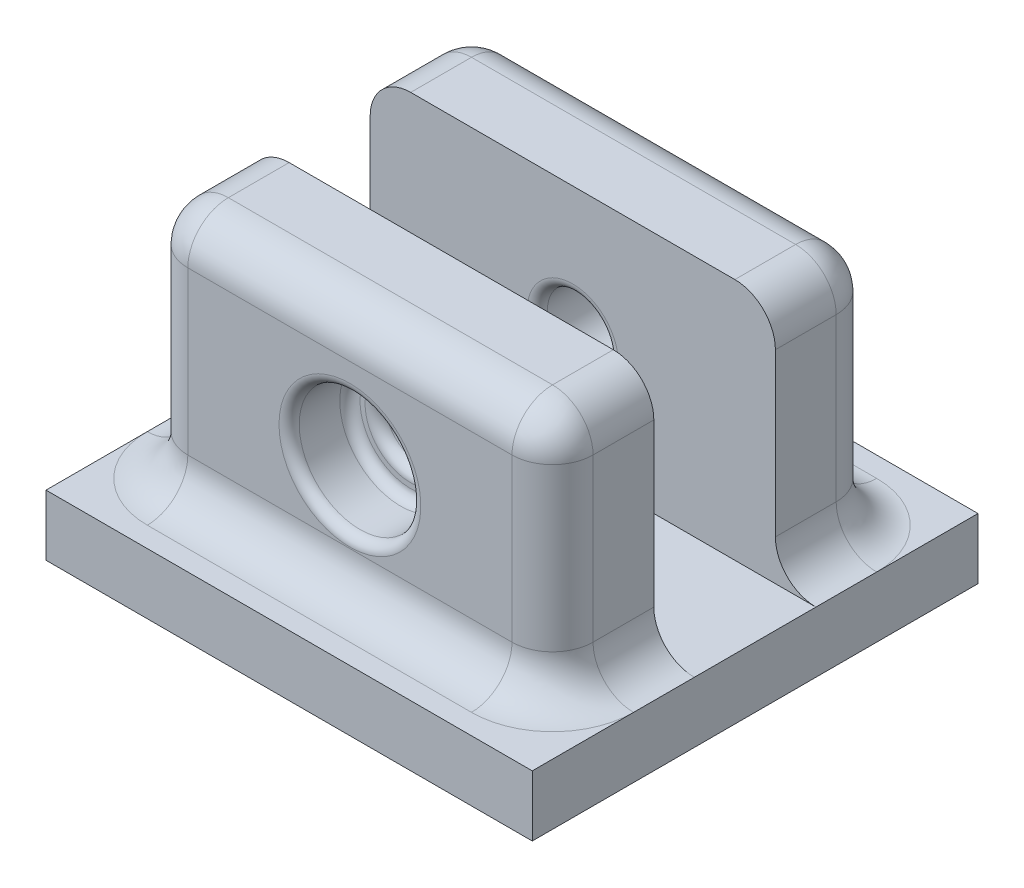
SolidWorks part; units mm, degrees
ref_plane "Front Plane" through (0, 0, 0) normal (0, 0, 1) x (1, 0, 0)
ref_plane "Top Plane" through (0, 0, 0) normal (0, 1, 0) x (1, 0, 0)
ref_plane "Right Plane" through (0, 0, 0) normal (1, 0, 0) x (0, 0, -1)
sketch "Sketch1" plane through (0, 0, 0) normal (0, 1, 0) x (1, 0, 0)
  line L0 (0, 0) -> (55.3653, 0) construction
  line L1 (-0.0683, -8) -> (19.9317, -8)
  line L2 (-0.0683, -8) -> (-0.0683, -3)
  line L3 (-0.0683, -3) -> (19.9317, -3)
  line L4 (19.9317, -8) -> (19.9317, -3)
  line L5 (-0.0683, -8) -> (19.9317, -3) construction
  line L6 (-0.0683, -3) -> (19.9317, -8) construction
  line L7 (-0.0683, 3) -> (19.9317, 8) construction
  line L8 (-0.0683, 8) -> (19.9317, 3) construction
  line L9 (19.9317, 8) -> (19.9317, 3)
  line L10 (-0.0683, 3) -> (19.9317, 3)
  line L11 (-0.0683, 8) -> (-0.0683, 3)
  line L12 (-0.0683, 8) -> (19.9317, 8)
  line L13 (9.9317, 27.2956) -> (9.9317, -24.6712) construction
  line L14 (-2.0683, -11) -> (21.9317, -11)
  line L15 (-2.0683, -11) -> (-2.0683, 11)
  line L16 (-2.0683, 11) -> (21.9317, 11)
  line L17 (21.9317, -11) -> (21.9317, 11)
  line L18 (-2.0683, -11) -> (21.9317, 11) construction
  line L19 (-2.0683, 11) -> (21.9317, -11) construction
  point P0 (9.9317, -5.5)
  point P12 (9.9317, 5.5)
  point P13 (9.9317, 0)
  dimension "D1" = 5
  dimension "D2" = 3
  dimension "D3" = 20
  dimension "D4" = 3
  dimension "D5" = 12
  dimension "D6" = 2
extrude "Boss-Extrude1" add sketch "Sketch1" along normal blind 15 contours L1 L4 L3 L2 | L12 L11 L10 L9 region at (9.9317, 0, 5.5) region at (9.9317, 0, -5.5)
sketch "Sketch2" plane through (0, 0, 8) normal (0, 0, 1) x (1, 0, 0)
  line L0 (9.9317, 15) -> (9.9317, 2.1254) construction
  line L3 (-0.0683, 10.7837) -> (17.1554, 10.7837) construction
  line L6 (-0.0683, 15) -> (-0.0683, 0) construction
  line L8 (-0.0683, 15) -> (19.9317, 15) construction
  circle A0 centre (9.9317, 8.5627) radius 1.75
  circle A1 centre (9.9317, 8.5627) radius 3
  point P8 (9.9317, 15)
  point P9 (9.9317, 9.2663)
  dimension "D1" = 6
  dimension "D2" = 3.5
extrude "Cut-Extrude1" cut sketch "Sketch2" against normal blind 19 contours A0 region at (9.9317, 8.5627, 8)
extrude "Cut-Extrude2" cut sketch "Sketch2<3>" against normal blind 3 contours A1 A0 region at (7.0166, 8.5627, 8)
sketch "Sketch2<3>" plane through (0, 0, 8) normal (0, 0, 1) x (1, 0, 0) same geometry as "Sketch2"
extrude "Boss-Extrude2" add sketch "Sketch1<3>" along normal blind 3
sketch "Sketch1<3>" plane through (0, 0, 0) normal (0, 1, 0) x (1, 0, 0) same geometry as "Sketch1"
fillet "Fillet1" radius 2 16 edges at (-0.0683, 3, -5.5) (9.9317, 3, -8) (9.9317, 3, 8) (-0.0683, 9, -8) (19.9317, 9, -8) (19.9317, 3, -5.5) (19.9317, 9, 8) (19.9317, 3, 5.5) (-0.0683, 3, 5.5) (-0.0683, 9, 8) (9.9317, 15, -8) (19.9317, 15, -5.5) (-0.0683, 15, -5.5) (19.9317, 15, 5.5) (-0.0683, 15, 5.5) (9.9317, 15, 8)
fillet "Fillet2" radius 0.5 6 edges at (8.1817, 8.5627, -3) (8.1817, 8.5627, -8) (8.1817, 8.5627, 3) (11.6817, 8.5627, 5) (12.9317, 8.5627, 5) (12.9317, 8.5627, 8)
